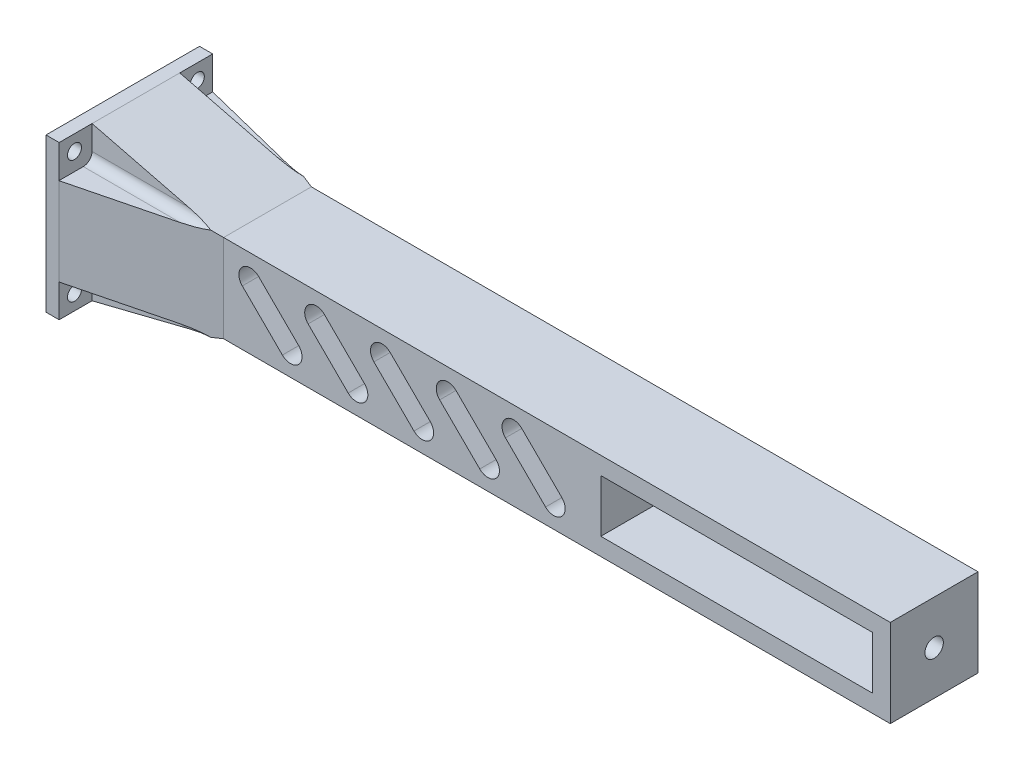
SolidWorks part; units mm, degrees
ref_plane "前视基准面" through (0, 0, 0) normal (0, 0, 1) x (1, 0, 0)
ref_plane "上视基准面" through (0, 0, 0) normal (0, 1, 0) x (1, 0, 0)
ref_plane "右视基准面" through (0, 0, 0) normal (1, 0, 0) x (0, 0, -1)
sketch "草图1" plane through (0, 0, 0) normal (1, 0, 0) x (0, 0, -1)
  line L1 (-10, 10) -> (10, 10)
  line L2 (-10, 10) -> (-10, -10)
  line L3 (-10, -10) -> (10, -10)
  line L4 (10, 10) -> (10, -10)
  line L5 (-10, 10) -> (10, -10) construction
  line L6 (-10, -10) -> (10, 10) construction
  point P0 (0, 0)
  dimension "D1" = 20
  dimension "D2" = 20
extrude "凸台-拉伸1" add sketch "草图1" along normal blind 182
sketch "草图2" plane through (0, 10, 0) normal (0, 1, 0) x (1, 0, 0)
  line L4 (160, 10) -> (160, -10)
  line L8 (0, 10) -> (0, -10) construction
  line L9 (0, -10) -> (160, -10) construction
  line L11 (160, 10) -> (0, 10) construction
  dimension "D1" = 160
  dimension "D2" = 160
sketch "草图3" plane through (0, 0, 0) normal (-1, 0, 0) x (0, 0, 1)
  line L1 (-17.5, 17.5) -> (17.5, 17.5)
  line L2 (-17.5, 17.5) -> (-17.5, -17.5)
  line L3 (-17.5, -17.5) -> (17.5, -17.5)
  line L4 (17.5, 17.5) -> (17.5, -17.5)
  line L5 (-17.5, 17.5) -> (17.5, -17.5) construction
  line L6 (-17.5, -17.5) -> (17.5, 17.5) construction
  point P0 (0, 0)
  dimension "D1" = 35
  dimension "D2" = 35
extrude "凸台-拉伸2" add sketch "草图3" along normal blind 3
sketch "草图4" plane through (182, 0, 0) normal (1, 0, 0) x (0, 0, -1)
  circle A0 centre (0, 0) radius 2.1
extrude "切除-拉伸2" cut sketch "草图4" against normal blind 23
sketch "草图5" plane through (-3, 0, 0) normal (-1, 0, 0) x (0, 0, 1)
  line L1 (-14, 14) -> (14, 14) construction
  line L2 (-14, 14) -> (-14, -14) construction
  line L3 (-14, -14) -> (14, -14) construction
  line L4 (14, 14) -> (14, -14) construction
  line L5 (-14, 14) -> (14, -14) construction
  line L6 (-14, -14) -> (14, 14) construction
  circle A0 centre (-14, 14) radius 1.6
  circle A1 centre (14, 14) radius 1.6
  circle A2 centre (-14, -14) radius 1.6
  circle A3 centre (14, -14) radius 1.6
  point P0 (0, 0)
  dimension "D1" = 28
  dimension "D2" = 28
extrude "切除-拉伸3" cut sketch "草图5" against normal up to next
sketch "草图6" plane through (0, 0, -10) normal (0, 0, -1) x (-1, 0, 0)
  line L0 (-30, 10) -> (0, 17.5)
  line L1 (-182, 10) -> (0, 10) construction
  line L2 (0, 17.5) -> (0, -17.5) construction
  line L3 (3, 17.5) -> (0, 17.5) construction
  line L4 (0, 17.5) -> (0, 10)
  line L5 (-182, 10) -> (0, 10) construction
  line L6 (0, 10) -> (-30, 10)
  line L7 (-27.2289, 0) -> (14.6216, 0) construction
  line L8 (0, -10) -> (-30, -10)
  line L9 (0, -17.5) -> (0, -10)
  line L10 (-30, -10) -> (0, -17.5)
  dimension "D1" = 30
extrude "凸台-拉伸3" add sketch "草图6" against normal up to surface (20 mm away) up to face at (91, 0, 10)
sketch "草图7" plane through (0, 10, 0) normal (0, 1, 0) x (1, 0, 0)
  line L0 (0, 10) -> (30, 10)
  line L1 (30, 10) -> (0, 17.5)
  line L2 (0, 10) -> (0, 17.5) construction
  line L3 (0, 17.5) -> (0, 10)
  line L4 (30, -10) -> (0, -10)
  line L5 (0, -10) -> (0, -17.5506)
  line L6 (0, -17.5506) -> (30, -10)
extrude "凸台-拉伸4" add sketch "草图7" against normal up to surface (20 mm away) up to face at (106, -10, 0)
fillet "圆角1" radius 2 4 edges at (15, 10, 10) (15, 10, -10) (15, -10, 10) (15, -10, -10)
sketch "草图8" plane through (0, 0, -10) normal (0, 0, -1) x (-1, 0, 0)
  line L0 (-182, -10) -> (-30, -10) construction
  line L1 (-116, -6) -> (-178, -6)
  line L2 (-116, -6) -> (-116, 6)
  line L3 (-116, 6) -> (-178, 6)
  line L4 (-178, -6) -> (-178, 6)
  line L5 (-116, -6) -> (-178, 6) construction
  line L6 (-116, 6) -> (-178, -6) construction
  line L7 (-182, -10) -> (-182, 10) construction
  line L8 (0, 10) -> (-160, 10) construction
  point P0 (-147, 0)
  dimension "D1" = 4
  dimension "D2" = 4
  dimension "D3" = 4
  dimension "D4" = 62
extrude "切除-拉伸4" cut sketch "草图8" against normal up to next
sketch "草图9" plane through (0, 0, 10) normal (0, 0, 1) x (1, 0, 0)
  line L0 (96.1123, 4.4332) -> (105.2516, -4.6454) construction
  line L1 (97.9642, 6.2975) -> (107.1035, -2.7812)
  line L2 (94.2604, 2.569) -> (103.3997, -6.5097)
  line L3 (81.1123, 4.4332) -> (90.2516, -4.6454) construction
  line L4 (82.9642, 6.2975) -> (92.1035, -2.7812)
  line L7 (79.2604, 2.569) -> (88.3997, -6.5097)
  line L8 (66.1123, 4.4332) -> (75.2516, -4.6454) construction
  line L11 (67.9642, 6.2975) -> (77.1035, -2.7812)
  line L12 (64.2604, 2.569) -> (73.3997, -6.5097)
  line L13 (51.1123, 4.4332) -> (60.2516, -4.6454) construction
  line L14 (52.9642, 6.2975) -> (62.1035, -2.7812)
  line L15 (49.2604, 2.569) -> (58.3997, -6.5097)
  line L16 (36.1123, 4.4332) -> (45.2516, -4.6454) construction
  line L17 (37.9642, 6.2975) -> (47.1035, -2.7812)
  line L18 (34.2604, 2.569) -> (43.3997, -6.5097)
  arc A0 (97.9642, 6.2975) -> (94.2604, 2.569) centre (96.1123, 4.4332) ccw
  arc A1 (103.3997, -6.5097) -> (107.1035, -2.7812) centre (105.2516, -4.6454) ccw
  arc A6 (82.9642, 6.2975) -> (79.2604, 2.569) centre (81.1123, 4.4332) ccw
  arc A7 (88.3997, -6.5097) -> (92.1035, -2.7812) centre (90.2516, -4.6454) ccw
  arc A8 (67.9642, 6.2975) -> (64.2604, 2.569) centre (66.1123, 4.4332) ccw
  arc A9 (73.3997, -6.5097) -> (77.1035, -2.7812) centre (75.2516, -4.6454) ccw
  arc A10 (52.9642, 6.2975) -> (49.2604, 2.569) centre (51.1123, 4.4332) ccw
  arc A11 (58.3997, -6.5097) -> (62.1035, -2.7812) centre (60.2516, -4.6454) ccw
  arc A12 (37.9642, 6.2975) -> (34.2604, 2.569) centre (36.1123, 4.4332) ccw
  arc A13 (43.3997, -6.5097) -> (47.1035, -2.7812) centre (45.2516, -4.6454) ccw
  point P2 (100.6819, -0.1061)
  point P11 (85.6819, -0.1061)
  point P18 (70.6819, -0.1061)
  point P25 (55.6819, -0.1061)
  point P32 (40.6819, -0.1061)
  dimension "D1" = 5
extrude "切除-拉伸6" cut sketch "草图9" against normal up to next
